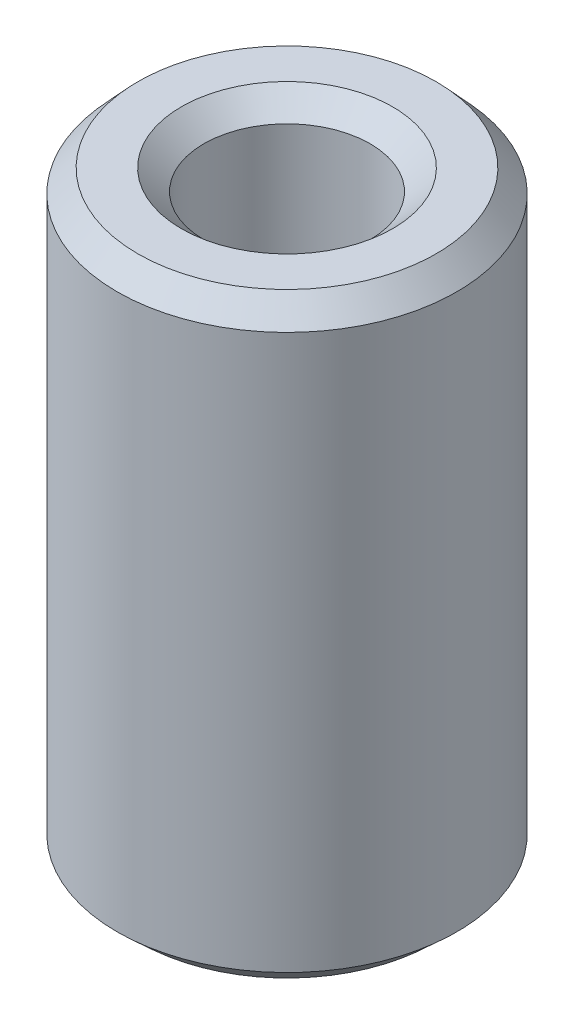
SolidWorks part; units mm, degrees
ref_plane "Front Plane" through (0, 0, 0) normal (0, 0, 1) x (1, 0, 0)
ref_plane "Top Plane" through (0, 0, 0) normal (0, 1, 0) x (1, 0, 0)
ref_plane "Right Plane" through (0, 0, 0) normal (1, 0, 0) x (0, 0, -1)
sketch "Sketch1" plane through (0, 0, 0) normal (0, 1, 0) x (1, 0, 0)
  circle A0 centre (0, 0) radius 15
  dimension "SLEEVE_OD" = 30
extrude "Boss-Extrude1" add sketch "Sketch1" along normal blind 52.7763
sketch "Sketch2" plane through (0, 0, 0) normal (0, 1, 0) x (1, 0, 0)
  circle A0 centre (0, 0) radius 7.3396
  dimension "BORE_D" = 14.6791
extrude "Cut-Extrude1" cut sketch "Sketch2" along normal through all
chamfer "Chamfer1" distance 1.99 angle 42.593 4 edges at (0, 52.7763, 7.3396) (0, 0, 7.3396) (0, 0, 15) (0, 52.7763, 15) first distance on face at (0, 52.7763, 7.3396) first distance on face at (0, 0, 7.3396) first distance on face at (0, 52.7763, 15)
